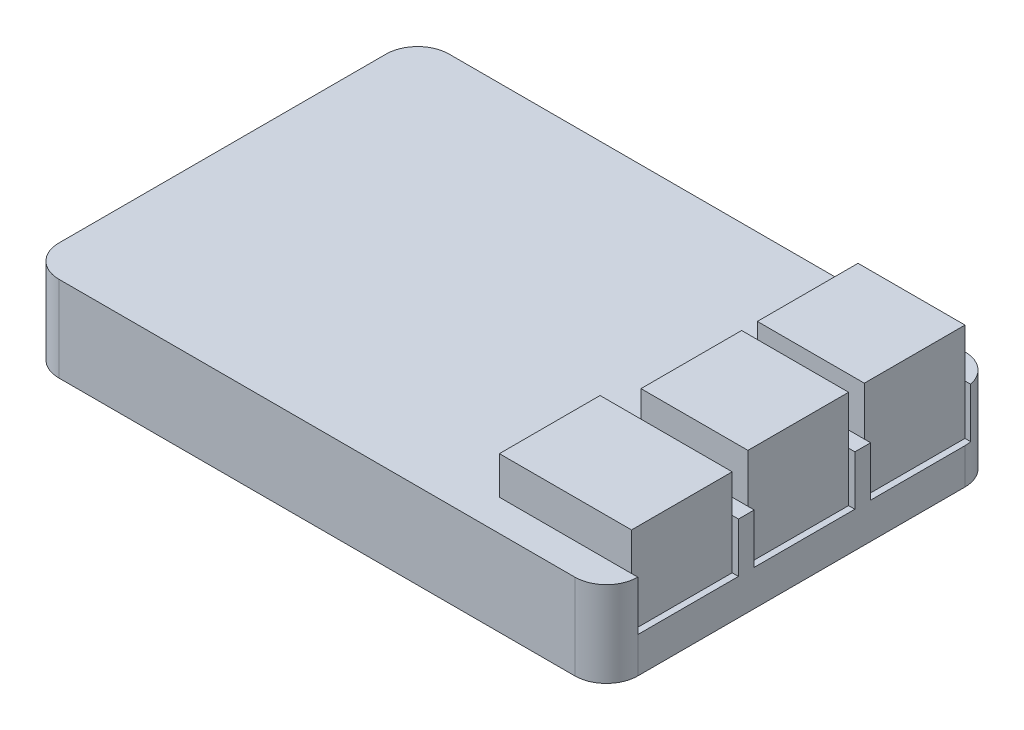
SolidWorks part; units mm, degrees
ref_plane "Front" through (0, 0, 0) normal (0, 0, 1) x (1, 0, 0)
ref_plane "Top" through (0, 0, 0) normal (0, 1, 0) x (1, 0, 0)
ref_plane "Right" through (0, 0, 0) normal (1, 0, 0) x (0, 0, -1)
sketch "Эскиз1" plane through (0, 0, 0) normal (0, 1, 0) x (1, 0, 0)
  line L1 (-46, 31) -> (46, 31)
  line L2 (-46, 31) -> (-46, -31)
  line L3 (-46, -31) -> (46, -31)
  line L4 (46, 31) -> (46, -31)
  line L5 (-46, 31) -> (46, -31) construction
  line L6 (-46, -31) -> (46, 31) construction
  arc A0 (-41, 31) -> (-46, 26) centre (-41, 26) ccw
  arc A1 (46, 26) -> (41, 31) centre (41, 26) ccw
  arc A2 (41, -31) -> (46, -26) centre (41, -26) ccw
  arc A3 (-46, -26) -> (-41, -31) centre (-41, -26) ccw
  point P0 (0, 0)
  dimension "D3" = 10
  dimension "D4" = 10
  dimension "D5" = 10
  dimension "D6" = 10
  dimension "D1" = 62
  dimension "D2" = 92
extrude "Бобышка-Вытянуть1" add sketch "Эскиз1" along normal blind 13.6 contours L2 A3 L3 A2 L4 A1 L1 A0 region at (0, 0, 0)
sketch "Эскиз3" plane through (46, 0, 0) normal (1, 0, 0) x (0, 0, -1)
  line L0 (26, 13.6) -> (-26, 13.6) construction
  line L1 (-26, 13.6) -> (-10, 13.6)
  line L2 (-26, 13.6) -> (-26, 5.7)
  line L3 (-26, 5.7) -> (-10, 5.7)
  line L4 (-10, 13.6) -> (-10, 5.7)
  line L5 (-7.5, 13.6) -> (8.5, 13.6)
  line L6 (-7.5, 13.6) -> (-7.5, 5.7)
  line L7 (-7.5, 5.7) -> (8.5, 5.7)
  line L8 (8.5, 13.6) -> (8.5, 5.7)
  line L9 (26, 0) -> (-26, 0) construction
  line L10 (11, 13.6) -> (27, 13.6)
  line L11 (11, 13.6) -> (11, 5.7)
  line L12 (11, 5.7) -> (27, 5.7)
  line L13 (27, 13.6) -> (27, 5.7)
  dimension "D1" = 16
  dimension "D2" = 5.7
  dimension "D3" = 2.5
  dimension "D4" = 2.5
  dimension "D5" = 16
extrude "Вырез-Вытянуть3" cut sketch "Эскиз3" against normal blind 1
sketch "Эскиз5" plane through (0, 13.6, 0) normal (0, 1, 0) x (1, 0, 0)
  line L1 (45, -10) -> (24, -10)
  line L2 (45, -10) -> (45, -26)
  line L3 (45, -26) -> (24, -26)
  line L4 (24, -10) -> (24, -26)
  line L5 (45, 8.5) -> (28, 8.5)
  line L6 (45, 8.5) -> (45, -7.5)
  line L7 (45, -7.5) -> (28, -7.5)
  line L8 (28, 8.5) -> (28, -7.5)
  line L9 (45, 27) -> (28, 27)
  line L10 (45, 27) -> (45, 11)
  line L11 (45, 11) -> (28, 11)
  line L12 (28, 27) -> (28, 11)
  line M6 (45, 11) -> (45, 27)
  line M16 (45, -26) -> (45, -10)
  line M20 (45, -7.5) -> (45, 8.5)
  dimension "D1" = 21
  dimension "D2" = 17
extrude "Бобышка-Вытянуть2" add sketch "Эскиз5" along normal blind 6 contours L1 L4 L3 M16 region at (34.5, 13.6, 18)
extrude "Бобышка-Вытянуть3" add sketch "Эскиз5<4>" along normal blind 7.7 contours L5 L8 L7 M20 | L9 L12 L11 M6 region at (36.5, 13.6, -0.5) region at (36.5, 13.6, -19)
sketch "Эскиз5<4>" plane through (0, 13.6, 0) normal (0, 1, 0) x (1, 0, 0) same geometry as "Эскиз5"
